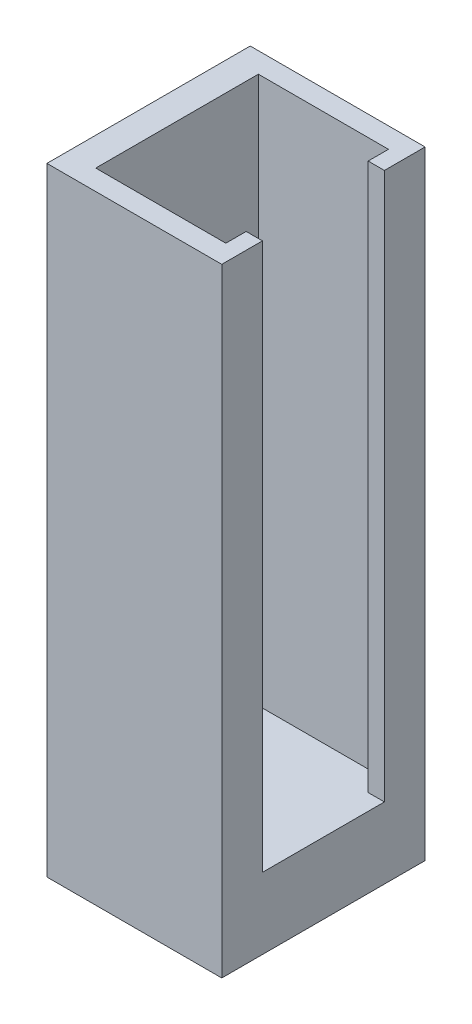
SolidWorks part; units mm, degrees
ref_plane "Front Plane" through (0, 0, 0) normal (0, 0, 1) x (1, 0, 0)
ref_plane "Top Plane" through (0, 0, 0) normal (0, 1, 0) x (1, 0, 0)
ref_plane "Right Plane" through (0, 0, 0) normal (1, 0, 0) x (0, 0, -1)
sketch "Sketch1" plane through (0, 0, 0) normal (0, 0, 1) x (1, 0, 0)
  line L1 (-2.15, 0) -> (2.15, 0)
  line L2 (-2.15, 0) -> (-2.15, 15.2)
  line L3 (-2.15, 15.2) -> (2.15, 15.2)
  line L4 (2.15, 0) -> (2.15, 15.2)
  point P4 (2.6645, 2.3315)
  point P5 (0, 0)
  dimension "D1" = 15.2
  dimension "D2" = 4.3
extrude "Boss-Extrude1" add sketch "Sketch1" along normal mid plane 5
sketch "Sketch3" plane through (0, 0, 0) normal (0, -1, 0) x (-1, 0, 0)
  line L0 (-2.15, -1.5) -> (-1.75, -1.5)
  line L1 (-2.15, -2.5) -> (-2.15, 2.5) construction
  line L2 (-1.75, -1.5) -> (-1.75, -2)
  line L3 (-1.75, -2) -> (1.45, -2)
  line L4 (1.45, -2) -> (1.45, 2)
  line L5 (1.45, 2) -> (-1.75, 2)
  line L6 (-1.75, 2) -> (-1.75, 1.5)
  line L7 (-1.75, 1.5) -> (-2.15, 1.5)
  line L8 (-2.15, 1.5) -> (-2.15, -1.5)
  line L9 (-2.15, 0) -> (1.45, 0) construction
  line L10 (2.15, -2.5) -> (-2.15, -2.5) construction
  line L11 (2.15, -2.5) -> (2.15, 2.5) construction
  point P12 (-2.15, -1.2376)
  point P14 (-2.15, 1.3768)
  point P19 (1.45, 1.7985)
  point P20 (-2.3671, 2)
  point P21 (-1.1583, 2)
  dimension "D1" = 3
  dimension "D2" = 0.5
  dimension "D3" = 0.7
  dimension "D4" = 3.2
extrude "Cut-Extrude1" cut sketch "Sketch3" against normal through all from offset 1.75 offset against normal yes
